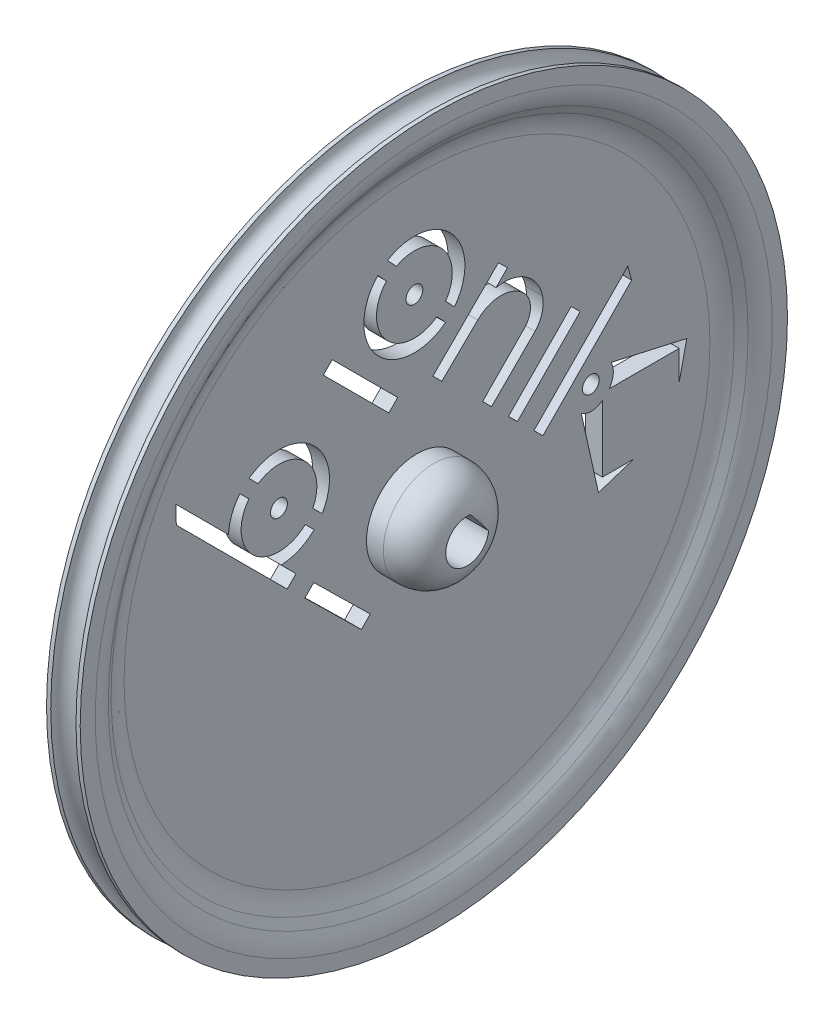
SolidWorks part; units mm, degrees
ref_plane "Płaszczyzna przednia" through (0, 0, 0) normal (0, 0, 1) x (1, 0, 0)
ref_plane "Płaszczyzna górna" through (0, 0, 0) normal (0, 1, 0) x (1, 0, 0)
ref_plane "Płaszczyzna prawa" through (0, 0, 0) normal (1, 0, 0) x (0, 0, -1)
sketch "Szkic1" plane through (0, 0, 0) normal (0, 0, 1) x (1, 0, 0)
  line L0 (6, -12.7789) -> (-2, -12.7789)
  line L1 (6, -12.7789) -> (6, -6.7789)
  line L2 (6, -6.7789) -> (0, -6.7789)
  line L3 (0, -6.7789) -> (0, 22.01)
  line L4 (2, 29.2211) -> (1.5, 29.2211)
  line L5 (2, 29.2211) -> (2, 27.4322)
  line L6 (-1.5, 29.2211) -> (-2, 29.2211)
  line L9 (-2, 29.2211) -> (-2, -12.7789)
  line L10 (0.6718, 24.2288) -> (1.3282, 25.2134)
  arc A0 (1.5, 29.2211) -> (-1.5, 29.2211) centre (0, 29.2211) cw
  arc A1 (2, 27.4322) -> (1.3282, 25.2134) centre (-2, 27.4322) cw
  arc A2 (0, 22.01) -> (0.6718, 24.2288) centre (4, 22.01) cw
  point P10 (2, 26.2211)
  point P17 (0, 23.2211)
  dimension "D6" = 1.5
  dimension "D9" = 4
  dimension "D10" = 4
  dimension "D1" = 8
  dimension "D2" = 6
  dimension "D3" = 42
  dimension "D4" = 4
  dimension "D5" = 3
  dimension "D7" = 0.5
  dimension "D8" = 30
  dimension "D11" = 2
revolve "Obrót1" add sketch "Szkic1" angle 360 about L0
sketch "Szkic4" plane through (6, 0, 0) normal (1, 0, 0) x (0, 0, -1)
  line L0 (0.3809, -10.2575) -> (2.5412, -12.9904)
  arc A0 (0.3809, -10.2575) -> (2.5412, -12.9904) centre (0, -12.7789) ccw
  circle A2 centre (0, -12.7789) radius 6 construction
extrude "Wytnij-wyciągnięcie8" cut sketch "Szkic4" against normal through all
sketch "Szkic5" plane through (0, 0, 0) normal (1, 0, 0) x (0, 0, -1)
  line L0 (112.1629, 275.1146) -> (679.4962, 275.1146) construction
  line L1 (-28.5833, 0.1628) -> (-15.4205, -13)
  line L2 (-15.4205, -13) -> (-14.3598, -11.9393)
  line L3 (-14.3598, -11.9393) -> (-16.128, -10.1712)
  line L4 (-22.3853, -3.9139) -> (-28.6529, 2.3537)
  line L5 (-28.6529, 2.3537) -> (-28.5833, 0.1628)
  line L6 (-11.1247, 6.8611) -> (-10.0641, 7.9218)
  line L7 (-10.0641, 7.9218) -> (-2.2859, 0.1436)
  line L8 (-2.2859, 0.1436) -> (-3.3466, -0.917)
  line L9 (-3.3466, -0.917) -> (-11.1247, 6.8611)
  line L10 (2.9478, -0.8115) -> (1.8871, 0.2492)
  line L11 (1.8871, 0.2492) -> (9.6653, 8.0274)
  line L12 (9.6653, 8.0274) -> (10.74, 6.9809)
  line L13 (10.74, 6.9809) -> (9.3969, 5.6017)
  line L14 (2.9478, -0.8115) -> (7.2101, 3.3578)
  line L15 (14.0203, -1.204) -> (8.8534, -6.3709)
  line L16 (8.8534, -6.3709) -> (7.7928, -5.3103)
  line L17 (7.7928, -5.3103) -> (12.7237, -0.2884)
  line L18 (18.3075, -0.7969) -> (19.3778, -1.8478)
  line L19 (19.3778, -1.8478) -> (11.9244, -9.4388)
  line L20 (11.9244, -9.4388) -> (10.8541, -8.3878)
  line L21 (10.8541, -8.3878) -> (18.3075, -0.7969)
  line L22 (13.8806, -11.3595) -> (25.0288, -0.0056)
  line L23 (25.0288, -0.0056) -> (25.4882, -1.6787)
  line L24 (25.4882, -1.6787) -> (14.9509, -12.4104)
  line L25 (14.9509, -12.4104) -> (13.8806, -11.3595)
  line L26 (-13.316, -14.9733) -> (-12.2651, -13.903)
  line L27 (-12.2651, -13.903) -> (-5.5501, -20.4964)
  line L28 (-5.5501, -20.4964) -> (-6.601, -21.5667)
  line L29 (-6.601, -21.5667) -> (-13.316, -14.9733)
  line L30 (23.0696, -8.9276) -> (32.0451, -10.9511)
  line L31 (32.0451, -10.9511) -> (31.1382, -14.9733)
  line L32 (31.1382, -14.9733) -> (31.1382, -11.5167)
  line L33 (31.1382, -11.5167) -> (22.8358, -11.5167)
  line L34 (19.5102, -12.4086) -> (21.5532, -21.5667)
  line L35 (21.5532, -21.5667) -> (25.7129, -20.206)
  line L36 (25.7129, -20.206) -> (22.0216, -20.206)
  line L37 (22.0216, -20.206) -> (22.0216, -12.291)
  line L38 (-12.217, -8.4872) -> (-13.2779, -7.4263)
  line L39 (-11.2736, -7.3093) -> (-12.3753, -6.2076)
  line L40 (-19.9685, -1.4471) -> (-21.0363, -0.3794)
  line L41 (-18.8718, -0.4225) -> (-19.9488, 0.6545)
  line L42 (-2.4343, 13.7136) -> (-3.4985, 14.8293)
  line L43 (-3.6256, 12.7892) -> (-4.6626, 13.8765)
  line L44 (3.3987, 7.1983) -> (4.4508, 6.0952)
  line L45 (2.3542, 6.1201) -> (3.3959, 5.0279)
  arc A0 (-2.4343, 13.7136) -> (3.3987, 7.1983) centre (-0.3103, 9.7464) cw
  circle A1 centre (-16.3911, -4.177) radius 1
  arc A2 (-3.6256, 12.7892) -> (2.3542, 6.1201) centre (-0.3103, 9.7464) ccw
  circle A3 centre (-0.3103, 9.7464) radius 1
  arc A6 (7.2101, 3.3578) -> (12.7237, 3.3578) centre (9.9669, 0.601) cw
  arc A7 (9.3969, 5.6017) -> (14.901, 2.0136) centre (10.3549, 1.0556) cw
  arc A8 (12.7237, 3.3578) -> (12.7237, -0.2884) centre (10.9006, 1.5347) cw
  arc A9 (14.901, 2.0136) -> (14.0203, -1.204) centre (11.4227, 1.2362) cw
  circle A10 centre (20.6456, -9.9783) radius 1
  arc A11 (23.0696, -8.9276) -> (22.8358, -11.5167) centre (20.7483, -10.023) cw
  arc A12 (22.0216, -12.291) -> (19.5102, -12.4086) centre (20.6874, -10.674) cw
  arc A13 (-21.0363, -0.3794) -> (-22.3853, -3.9139) centre (-16.3911, -4.177) ccw
  arc A14 (-19.9488, 0.6545) -> (-11.2736, -7.3093) centre (-16.3911, -4.177) cw
  arc A15 (-12.3753, -6.2076) -> (-18.8718, -0.4225) centre (-16.3911, -4.177) ccw
  arc A16 (-19.9685, -1.4471) -> (-13.2779, -7.4263) centre (-16.3911, -4.177) ccw
  arc A17 (-12.217, -8.4872) -> (-16.128, -10.1712) centre (-16.3911, -4.177) cw
  arc A18 (-3.4985, 14.8293) -> (4.4508, 6.0952) centre (-0.3103, 9.7464) cw
  arc A19 (-4.6626, 13.8765) -> (3.3959, 5.0279) centre (-0.3103, 9.7464) ccw
  point P71 (0, -13)
  dimension "D4" = 1.5
  dimension "D11" = 1.5
  dimension "D12" = 2
  dimension "D13" = 2
  dimension "D14" = 1.5
  dimension "D15" = 1.5
  dimension "D19" = 11
  dimension "D23" = 1.5
  dimension "D24" = 1.5
  dimension "D25" = 6
  dimension "D26" = 6
  dimension "D1" = 1.5
  dimension "D2" = 1.5
  dimension "D3" = 1.5
  dimension "D5" = 1.5
  dimension "D6" = 1.5
  dimension "D7" = 1.5
  dimension "D8" = 1.5
  dimension "D9" = 1.5
  dimension "D10" = 1.5
  dimension "D16" = 1.5
  dimension "D17" = 1.5
  dimension "D18" = 1.5
  dimension "D20" = 11
  dimension "D21" = 10.6384
  dimension "D22" = 1.5
  dimension "D27" = 0.524
extrude "Wytnij-wyciągnięcie9" cut sketch "Szkic5" against normal through all
fillet "Zaokrąglenie1" radius 4 1 edges at (6, -6.7789, 0)
